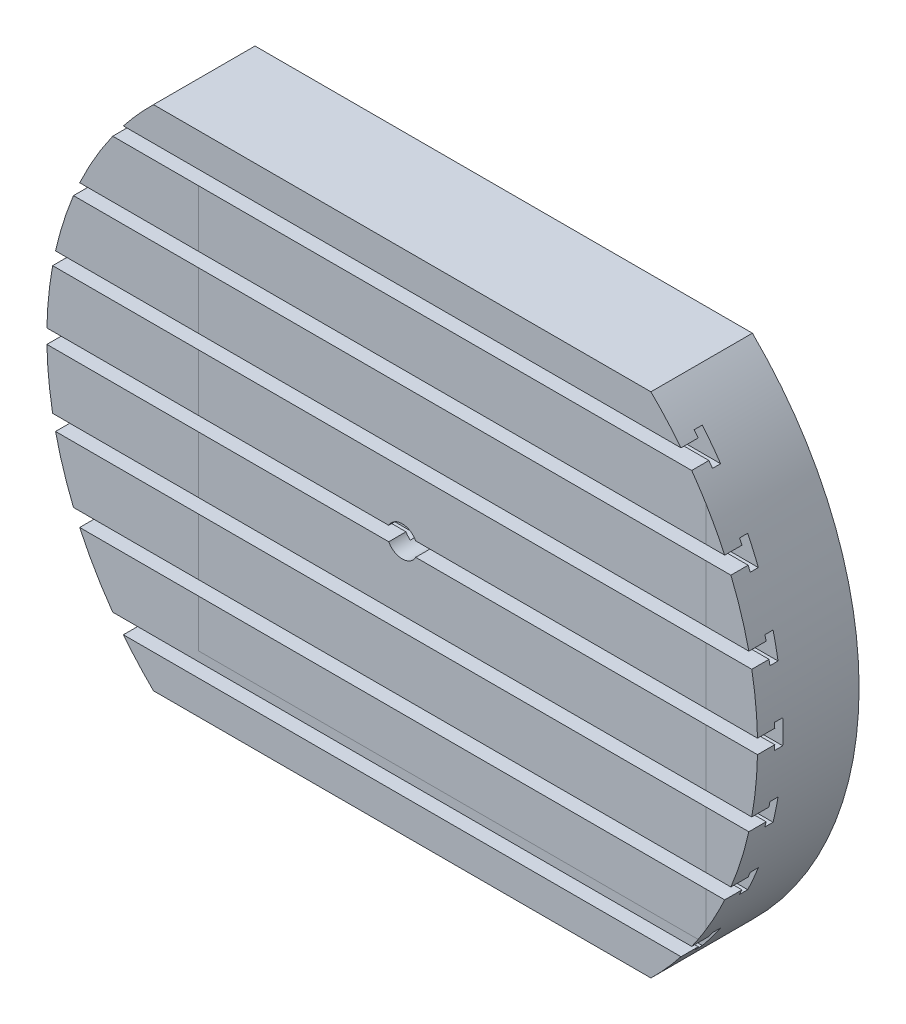
SolidWorks part; units mm, degrees
material "Plain Carbon Steel"
ref_plane "Front Plane" through (0, 0, 0) normal (0, 0, 1) x (1, 0, 0)
ref_plane "Top Plane" through (0, 0, 0) normal (0, 1, 0) x (1, 0, 0)
ref_plane "Right Plane" through (0, 0, 0) normal (1, 0, 0) x (0, 0, -1)
sketch "Sketch1" plane through (0, 0, 0) normal (0, 0, 1) x (1, 0, 0)
  circle A0 centre (0, 0) radius 350
  circle A1 centre (0, 0) radius 15
  dimension "D1" = 700
  dimension "D2" = 30
extrude "Boss-Extrude1" add sketch "Sketch1" along normal blind 100
sketch "Sketch2" plane through (0, 0, 0) normal (1, 0, 0) x (0, 0, -1)
  line L0 (-100, 7) -> (-83, 7)
  line L1 (-100, 350) -> (-100, -350) construction
  line L2 (-83, 7) -> (-83, 12)
  line L3 (-83, 12) -> (-75, 12)
  line L4 (-75, 12) -> (-75, -12)
  line L5 (-75, -12) -> (-83, -12)
  line L6 (-83, -12) -> (-83, -7)
  line L7 (-83, -7) -> (-100, -7)
  line L8 (-100, -7) -> (-100, 7)
  line L9 (-100, 0) -> (-75, 0) construction
  line L10 (-83, 7) -> (-83, -7) construction
  line L11 (-100, -77) -> (-100, -63)
  line L12 (-100, -63) -> (-83, -63)
  line L13 (-83, -77) -> (-100, -77)
  line L14 (-83, -82) -> (-83, -77)
  line L15 (-75, -82) -> (-83, -82)
  line L16 (-75, -58) -> (-75, -82)
  line L17 (-83, -58) -> (-75, -58)
  line L18 (-83, -63) -> (-83, -58)
  line L19 (-100, -147) -> (-100, -133)
  line L20 (-100, -133) -> (-83, -133)
  line L21 (-83, -147) -> (-100, -147)
  line L22 (-83, -152) -> (-83, -147)
  line L23 (-75, -152) -> (-83, -152)
  line L24 (-75, -128) -> (-75, -152)
  line L25 (-83, -128) -> (-75, -128)
  line L26 (-83, -133) -> (-83, -128)
  line L27 (-100, -217) -> (-100, -203)
  line L28 (-100, -203) -> (-83, -203)
  line L29 (-83, -217) -> (-100, -217)
  line L30 (-83, -222) -> (-83, -217)
  line L31 (-75, -222) -> (-83, -222)
  line L32 (-75, -198) -> (-75, -222)
  line L33 (-83, -198) -> (-75, -198)
  line L34 (-83, -203) -> (-83, -198)
  line L43 (0, -350) -> (0, 350) construction
  line L44 (-100, -350) -> (0, -350)
  line L45 (-100, -350) -> (-100, -250)
  line L46 (-100, -250) -> (0, -250)
  line L47 (0, -350) -> (0, -250)
  line L48 (-100, 63) -> (-100, 77)
  line L49 (-100, 350) -> (0, 350)
  line L50 (-100, 350) -> (-100, 250)
  line L51 (-100, 250) -> (0, 250)
  line L52 (0, 350) -> (0, 250)
  line L53 (-83, 63) -> (-100, 63)
  line L54 (-83, 58) -> (-83, 63)
  line L55 (-75, 58) -> (-83, 58)
  line L56 (-75, 82) -> (-75, 58)
  line L57 (-83, 82) -> (-75, 82)
  line L58 (-83, 77) -> (-83, 82)
  line L59 (-100, 77) -> (-83, 77)
  line L60 (-100, 133) -> (-100, 147)
  line L61 (-83, 133) -> (-100, 133)
  line L62 (-83, 128) -> (-83, 133)
  line L63 (-75, 128) -> (-83, 128)
  line L64 (-75, 152) -> (-75, 128)
  line L65 (-83, 152) -> (-75, 152)
  line L66 (-83, 147) -> (-83, 152)
  line L67 (-100, 147) -> (-83, 147)
  line L68 (-100, 203) -> (-100, 217)
  line L69 (-83, 203) -> (-100, 203)
  line L70 (-83, 198) -> (-83, 203)
  line L71 (-75, 198) -> (-83, 198)
  line L72 (-75, 222) -> (-75, 198)
  line L73 (-83, 222) -> (-75, 222)
  line L74 (-83, 217) -> (-83, 222)
  line L75 (-100, 217) -> (-83, 217)
  dimension "D1" = 14
  dimension "D2" = 24
  dimension "D3" = 17
  dimension "D4" = 8
  dimension "D6" = 56
  dimension "D7" = 100
  dimension "D8" = 100
  dimension "D10" = 56
  dimension "D5" = 4
  dimension "D9" = 4
extrude "Cut-Extrude1" cut sketch "Sketch2" against normal mid plane 1000
sketch "Sketch3" plane through (0, 0, 100) normal (0, 0, 1) x (1, 0, 0)
  line L1 (-200.66, -193.7836) -> (299.34, -193.7836)
  line L2 (-200.66, -193.7836) -> (-200.66, 206.2164)
  line L3 (-200.66, 206.2164) -> (299.34, 206.2164)
  line L4 (299.34, -193.7836) -> (299.34, 206.2164)
  line L5 (0, 206.2164) -> (0, -193.7836) construction
  line L6 (-200.66, 0) -> (299.34, 0) construction
  dimension "D1" = 500
  dimension "D2" = 400
  dimension "D3" = 200.66
  dimension "D4" = 193.7836
split line "Split Line1"
